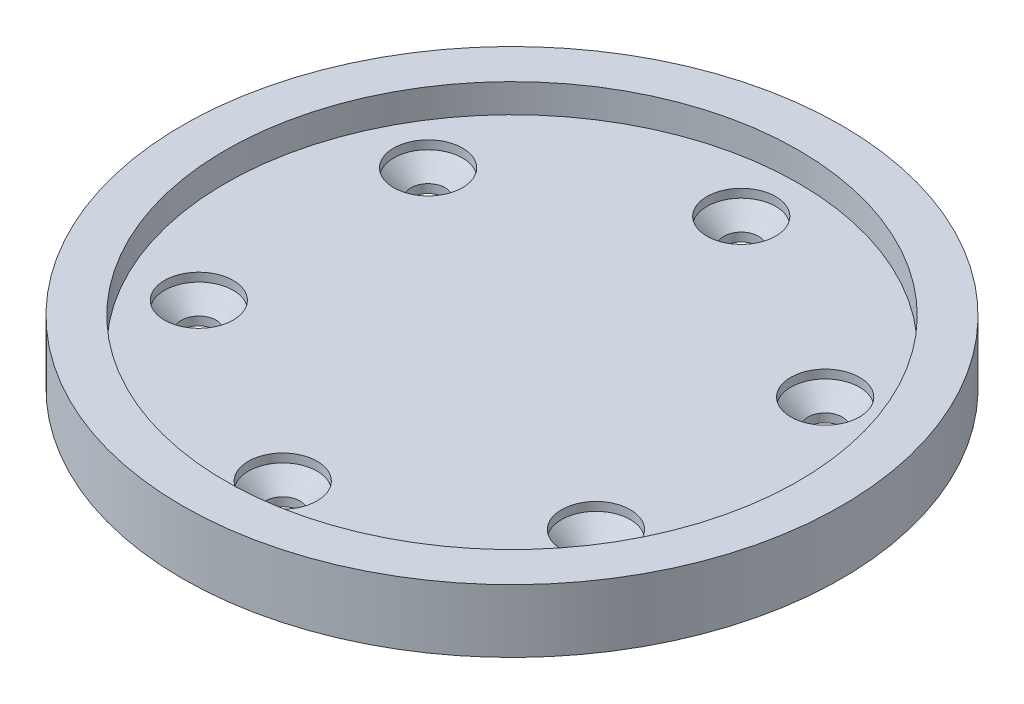
SolidWorks part; units mm, degrees
material "PBT General Purpose"
ref_plane "Front Plane" through (0, 0, 0) normal (0, 0, 1) x (1, 0, 0)
ref_plane "Top Plane" through (0, 0, 0) normal (0, 1, 0) x (1, 0, 0)
ref_plane "Right Plane" through (0, 0, 0) normal (1, 0, 0) x (0, 0, -1)
sketch "Sketch1" plane through (0, 0, 0) normal (0, 0, 1) x (1, 0, 0)
  line L0 (0, 0) -> (0, 21.4941) construction
  line L1 (50, 5.4786) -> (50, 10.4786)
  line L2 (50, 10.4786) -> (57.5, 10.4786)
  line L9 (50, 5.4786) -> (0, 5.4786)
  line L10 (0, -0.5214) -> (0, 5.4786)
  line L11 (0, -0.5214) -> (57.5, -0.5214)
  line L12 (57.5, -0.5214) -> (57.5, 10.4786)
  dimension "D1" = 0.5214
  dimension "D2" = 50
  dimension "D5" = 7.5
  dimension "D3" = 6
  dimension "D7" = 5
revolve "Revolve1" add sketch "Sketch1" angle 360 about L0
sketch "Sketch2" plane through (0, 5.4786, 0) normal (0, 1, 0) x (1, 0, 0)
  line L0 (0, 0) -> (0, 40) construction
  circle A0 centre (0, 40) radius 3
  circle A6 centre (34.641, 20) radius 3
  circle A7 centre (34.641, -20) radius 3
  circle A8 centre (0, -40) radius 3
  circle A9 centre (-34.641, -20) radius 3
  circle A10 centre (-34.641, 20) radius 3
  point P31 (0, 0)
  dimension "D1" = 6
  dimension "D2" = 40
  dimension "D3" = 6
extrude "Cut-Extrude1" cut sketch "Sketch2" against normal through all
sketch "Sketch3" plane through (0, 5.4786, 0) normal (0, 1, 0) x (1, 0, 0)
  circle A0 centre (0, 40) radius 6
  circle A1 centre (34.641, 20) radius 6
  circle A2 centre (34.641, -20) radius 6
  circle A3 centre (0, -40) radius 6
  circle A4 centre (-34.641, -20) radius 6
  circle A5 centre (-34.641, 20) radius 6
  point P3 (0, 0)
  point P18 (0, 0)
  dimension "D1" = 12
  dimension "D2" = 6
extrude "Cut-Extrude2" cut sketch "Sketch3" against normal blind 1.5
chamfer "Chamfer1" distance 3 angle 45 6 edges at (-34.641, 3.9786, -17) (-34.641, 3.9786, 23) (0, 3.9786, 43) (0, 3.9786, -37) (34.641, 3.9786, -17) (34.641, 3.9786, 23)
sketch3d "3DSketch1"
  point P0 (-57, 29.4786, 57)
